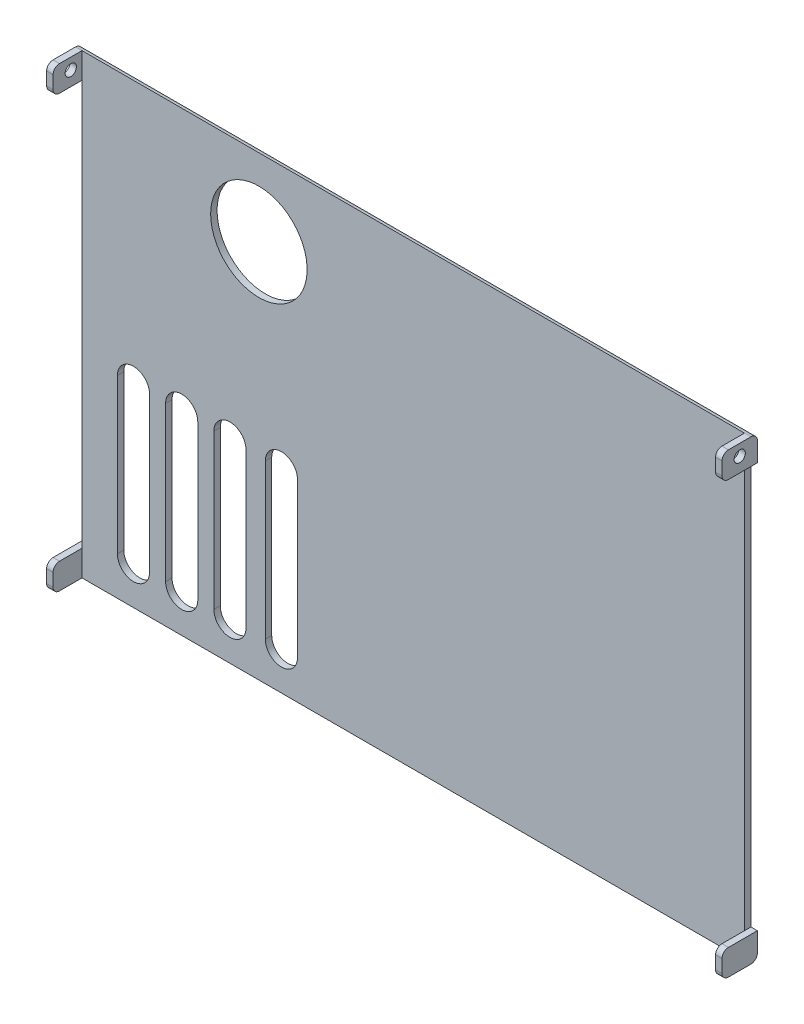
SolidWorks part; units mm, degrees
ref_plane "Front Plane" through (0, 0, 0) normal (0, 0, 1) x (1, 0, 0)
ref_plane "Top Plane" through (0, 0, 0) normal (0, 1, 0) x (1, 0, 0)
ref_plane "Right Plane" through (0, 0, 0) normal (1, 0, 0) x (0, 0, -1)
sketch "Sketch1" plane through (0, 0, 0) normal (0, 0, 1) x (1, 0, 0)
  line L1 (110, -85.3987) -> (-100, -85.3987)
  line L2 (110, -85.3987) -> (110, 56.6013)
  line L3 (110, 56.6013) -> (-100, 56.6013)
  line L4 (-100, -85.3987) -> (-100, 56.6013)
  line L5 (110, -85.3987) -> (-100, 56.6013) construction
  line L6 (110, 56.6013) -> (-100, -85.3987) construction
  point P0 (5, -14.3987)
  dimension "D1" = 210
  dimension "D2" = 142
extrude "body" add sketch "Sketch1" along normal blind 2
sketch "Sketch2" plane through (0, 0, 2) normal (0, 0, 1) x (1, 0, 0)
  text T0 "this is a test"
extrude "Boss-Extrude2" [suppressed] add sketch "Sketch2" along normal blind 1
sketch "Sketch3" plane through (0, 0, 0) normal (0, 0, -1) x (-1, 0, 0)
  line L0 (100, -49.3987) -> (-110, -49.3987) construction
  line L1 (100, 56.6013) -> (100, -85.3987) construction
  line L2 (-110, -85.3987) -> (-110, 56.6013) construction
  line L3 (67, -73.3987) -> (67, -25.3987) construction
  line L4 (62, -73.3987) -> (62, -25.3987)
  line L5 (72, -73.3987) -> (72, -25.3987)
  line L6 (100, -25.3987) -> (-110, -25.3987) construction
  line L7 (82, -73.3987) -> (82, -25.3987) construction
  line L8 (100, -73.3987) -> (-110, -73.3987) construction
  line L9 (77, -73.3987) -> (77, -25.3987)
  line L10 (87, -73.3987) -> (87, -25.3987)
  line L11 (52, -73.3987) -> (52, -25.3987) construction
  line L12 (47, -73.3987) -> (47, -25.3987)
  line L13 (57, -73.3987) -> (57, -25.3987)
  line L14 (36, -73.3987) -> (36, -25.3987) construction
  line L15 (31, -73.3987) -> (31, -25.3987)
  line L16 (41, -73.3987) -> (41, -25.3987)
  line L18 (-110, 56.6013) -> (100, 56.6013) construction
  line L19 (100, -85.3987) -> (-110, -85.3987) construction
  circle A0 centre (43, 32.6013) radius 15
  arc A1 (62, -73.3987) -> (72, -73.3987) centre (67, -73.3987) ccw
  arc A2 (72, -25.3987) -> (62, -25.3987) centre (67, -25.3987) ccw
  arc A3 (77, -73.3987) -> (87, -73.3987) centre (82, -73.3987) ccw
  arc A4 (87, -25.3987) -> (77, -25.3987) centre (82, -25.3987) ccw
  arc A5 (47, -73.3987) -> (57, -73.3987) centre (52, -73.3987) ccw
  arc A6 (57, -25.3987) -> (47, -25.3987) centre (52, -25.3987) ccw
  arc A7 (31, -73.3987) -> (41, -73.3987) centre (36, -73.3987) ccw
  arc A8 (41, -25.3987) -> (31, -25.3987) centre (36, -25.3987) ccw
  point P10 (67, -49.3987)
  point P21 (82, -49.3987)
  point P27 (52, -49.3987)
  point P34 (36, -49.3987)
  dimension "D1" = 30
  dimension "D2" = 24
  dimension "D3" = 57
  dimension "D4" = 13
  dimension "D5" = 12
  dimension "D6" = 24
  dimension "D8" = 10
  dimension "D9" = 10
  dimension "D10" = 10
  dimension "D11" = 10
  dimension "D12" = 5
  dimension "D13" = 56
  dimension "D14" = 5
extrude "Cut-Extrude1" cut sketch "Sketch3" against normal through all
fillet "Fillet1" radius 2 2 edges at (5, 56.6013, 0) (5, -85.3987, 0)
sketch "Sketch4" plane through (0, 0, 0) normal (0, 0, -1) x (-1, 0, 0)
  line L3 (19.8538, -13.4368) -> (95.048, -13.4368)
  line L4 (19.8538, -13.4368) -> (19.8538, -81.1257)
  line L5 (19.8538, -81.1257) -> (95.048, -81.1257)
  line L6 (95.048, -13.4368) -> (95.048, -81.1257)
  line L7 (-58.6903, 11.5462) -> (17.1179, 11.5462)
  line L8 (-58.6903, 11.5462) -> (-58.6903, -81.1257)
  line L9 (-58.6903, -81.1257) -> (17.1179, -81.1257)
  line L10 (17.1179, 11.5462) -> (17.1179, -81.1257)
  circle A0 centre (43, 32.6013) radius 20.0134
extrude "Cut-Extrude2" cut sketch "Sketch4" against normal blind 0.01
sketch "Sketch6" plane through (0, 0, 2) normal (0, 0, 1) x (1, 0, 0)
  line L0 (-100, 56.6013) -> (-100, -85.3987) construction
  line L1 (-100, 48.6013) -> (-98, 48.6013)
  line L2 (-100, 48.6013) -> (-100, -77.3987)
  line L3 (-100, -77.3987) -> (-98, -77.3987)
  line L4 (-98, 48.6013) -> (-98, -77.3987)
  line L5 (-100, 48.6013) -> (110, 48.6013) construction
  line L6 (110, -85.3987) -> (110, 56.6013) construction
  line L7 (-100, -77.3987) -> (110, -77.3987) construction
  line L8 (110, -77.3987) -> (128.428, -55.3387) construction
  line L9 (110, 56.6013) -> (-100, 56.6013) construction
  line L10 (110, 48.6013) -> (108, 48.6013)
  line L11 (110, 48.6013) -> (110, -77.3987)
  line L12 (110, -77.3987) -> (108, -77.3987)
  line L13 (108, 48.6013) -> (108, -77.3987)
  line L14 (-100, -85.3987) -> (110, -85.3987) construction
  dimension "D1" = 8
  dimension "D2" = 8
  dimension "D3" = 2
  dimension "D4" = 2
extrude "Cut-Extrude3" cut sketch "Sketch6" against normal through all
sketch "Sketch7" plane through (0, 0, 2) normal (0, 0, 1) x (1, 0, 0)
  line L0 (-98, 48.6013) -> (-100, 48.6013) construction
  line L1 (-100, 56.6013) -> (-98, 56.6013)
  line L2 (-100, 56.6013) -> (-100, 48.6013)
  line L3 (-100, 48.6013) -> (-98, 48.6013)
  line L4 (-98, 56.6013) -> (-98, 48.6013)
  line L5 (-100, -77.3987) -> (-100, -85.3987) construction
  line L6 (-100, -77.3987) -> (-98, -77.3987)
  line L7 (-100, -77.3987) -> (-100, -85.3987)
  line L8 (-100, -85.3987) -> (-98, -85.3987)
  line L9 (-98, -77.3987) -> (-98, -85.3987)
  line L10 (-100, -85.3987) -> (110, -85.3987) construction
  line L11 (110, 56.6013) -> (-100, 56.6013) construction
  line L12 (110, 48.6013) -> (108, 48.6013)
  line L13 (110, 48.6013) -> (110, 56.6013)
  line L14 (110, 56.6013) -> (108, 56.6013)
  line L15 (108, 48.6013) -> (108, 56.6013)
  line L17 (110, -85.3987) -> (108, -85.3987)
  line L18 (110, -85.3987) -> (110, -77.3987)
  line L19 (110, -77.3987) -> (108, -77.3987)
  line L20 (108, -85.3987) -> (108, -77.3987)
  dimension "D1" = 2
  dimension "D2" = 2
  dimension "D3" = 2
  dimension "D4" = 2
extrude "Boss-Extrude4" add sketch "Sketch7" along normal blind 9
fillet "Fillet3" radius 2 8 edges at (109, -85.3987, 11) (109, -77.3987, 11) (109, 48.6013, 11) (109, 56.6013, 11) (-99, -85.3987, 11) (-99, -77.3987, 11) (-99, 48.6013, 11) (-99, 56.6013, 11)
sketch "Sketch8" plane through (110, 0, 0) normal (1, 0, 0) x (0, 0, -1)
  line L2 (0, 48.6013) -> (0, 54.6013) construction
  line L3 (-9, 56.6013) -> (-2, 56.6013) construction
  circle A0 centre (-5.5, 53.1013) radius 1.75
  point P6 (0, 52.7613)
  dimension "D1" = 3.5
  dimension "D2" = 5.5
  dimension "D3" = 3.5
extrude "Cut-Extrude4" cut sketch "Sketch8" against normal through all
fillet "Fillet4" radius 5 4 edges at (-95.048, -81.1257, 0.005) (-19.8538, -81.1257, 0.005) (-95.048, -13.4368, 0.005) (-19.8538, -13.4368, 0.005)
fillet "Fillet5" radius 2 4 edges at (58.6903, -81.1257, 0.005) (-17.1179, -81.1257, 0.005) (-17.1179, 11.5462, 0.005) (58.6903, 11.5462, 0.005)
